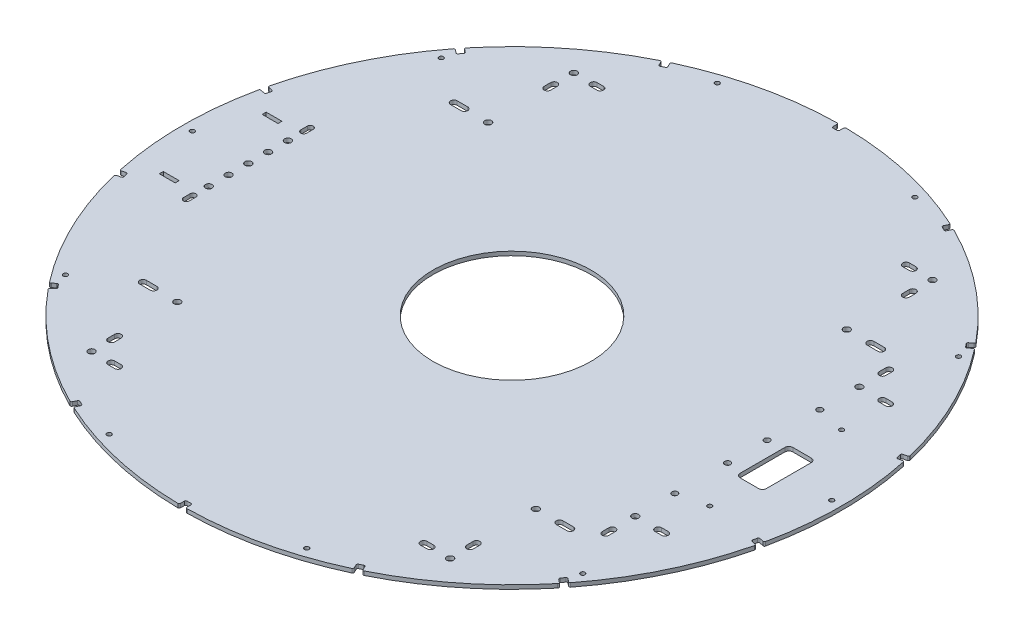
SolidWorks part; units mm, degrees
ref_plane "Front Plane" through (0, 0, 0) normal (0, 0, 1) x (1, 0, 0)
ref_plane "Top Plane" through (0, 0, 0) normal (0, 1, 0) x (1, 0, 0)
ref_plane "Right Plane" through (0, 0, 0) normal (1, 0, 0) x (0, 0, -1)
sketch "Sketch1" plane through (0, 0, 0) normal (0, 1, 0) x (1, 0, 0)
  circle A0 centre (0, 0) radius 250
extrude "Boss-Extrude1" add sketch "Sketch1" along normal blind 3
sketch "Sketch11" plane through (0, 3, 0) normal (0, 1, 0) x (1, 0, 0)
  line L1 (1.5, 245) -> (-1.5, 245)
  line L2 (2.5, 246) -> (2.5, 255)
  line L3 (2.5, 255) -> (-2.5, 255)
  line L4 (-2.5, 246) -> (-2.5, 255)
  line L5 (2.5, 245) -> (-2.5, 255) construction
  line L6 (2.5, 255) -> (-2.5, 245) construction
  circle A0 centre (0, 0) radius 250 construction
  arc A1 (2.5, 246) -> (1.5, 245) centre (1.5, 246) cw
  arc A2 (-1.5, 245) -> (-2.5, 246) centre (-1.5, 246) cw
  point P0 (0, 250)
  dimension "D3" = 1
  dimension "D1" = 10
  dimension "D2" = 5
extrude "Cut-Extrude5" cut sketch "Sketch11" against normal blind 4
fillet "Fillet1" radius 1 2 edges at (2.5, 1.5, -249.9875) (-2.5, 1.5, -249.9875)
pattern_circular "CirPattern1" count 14 over 360 about axis through (0, 3, 0) along (0, -1, 0) of "Cut-Extrude5", "Fillet1"
sketch "Sketch20" plane through (0, 0, 0) normal (0, -1, 0) x (1, 0, 0)
  line L0 (-166.5, -117.9) -> (-148.647, -117.9) construction
  line L1 (-162, -117.9) -> (-154, -117.9) construction
  line L2 (-162, -115.4) -> (-154, -115.4)
  line L3 (-162, -120.4) -> (-154, -120.4)
  line L4 (0, -1.65) -> (0, 1.65) construction
  line L5 (166.5, -117.9) -> (148.647, -117.9) construction
  line L6 (162, -117.9) -> (154, -117.9) construction
  line L7 (162, -115.4) -> (154, -115.4)
  line L8 (162, -120.4) -> (154, -120.4)
  line L9 (1.65, 0) -> (-1.65, 0) construction
  line L10 (162, 117.9) -> (154, 117.9) construction
  line L11 (162, 115.4) -> (154, 115.4)
  line L12 (162, 120.4) -> (154, 120.4)
  line L13 (-162, 117.9) -> (-154, 117.9) construction
  line L14 (-162, 115.4) -> (-154, 115.4)
  line L15 (-162, 120.4) -> (-154, 120.4)
  line L16 (-166.5, 117.9) -> (-148.647, 117.9) construction
  line L17 (166.5, 117.9) -> (148.647, 117.9) construction
  arc A0 (-164, -115.4) -> (-164, -120.4) centre (-164, -117.9) ccw construction
  arc A1 (-162, -115.4) -> (-162, -120.4) centre (-162, -117.9) ccw
  arc A2 (-154, -120.4) -> (-154, -115.4) centre (-154, -117.9) ccw
  arc A3 (162, -115.4) -> (162, -120.4) centre (162, -117.9) cw
  arc A4 (154, -120.4) -> (154, -115.4) centre (154, -117.9) cw
  arc A5 (162, 115.4) -> (162, 120.4) centre (162, 117.9) ccw
  arc A6 (154, 120.4) -> (154, 115.4) centre (154, 117.9) ccw
  arc A7 (-162, 115.4) -> (-162, 120.4) centre (-162, 117.9) cw
  arc A8 (-154, 120.4) -> (-154, 115.4) centre (-154, 117.9) cw
  point P8 (-158, -117.9)
  point P20 (158, -117.9)
  point P29 (158, 117.9)
  point P36 (-158, 117.9)
  dimension "D1" = 2.5
  dimension "D2" = 8
  dimension "D3" = 158
extrude "Cut-Extrude14" cut sketch "Sketch20" against normal blind 14
sketch "Sketch22" plane through (0, 3, 0) normal (0, 1, 0) x (1, 0, 0)
  line L0 (-1.65, 0) -> (1.65, 0) construction
  line L1 (0, -1.65) -> (0, 1.65) construction
  circle A0 centre (-136, -117.9) radius 2.5
  circle A1 centre (-136, 117.9) radius 2.5
  circle A2 centre (136, 117.9) radius 2.5
  circle A3 centre (136, -117.9) radius 2.5
  circle A4 centre (-136, 182.9) radius 2.5
  circle A5 centre (136, 182.9) radius 2.5
  circle A6 centre (-136, -182.9) radius 2.5
  circle A7 centre (136, -182.9) radius 2.5
  dimension "D1" = 2
extrude "Cut-Extrude16" cut sketch "Sketch22" against normal blind 14
sketch "Sketch26" plane through (0, 3, 0) normal (0, 1, 0) x (1, 0, 0)
  line L0 (-136, 162.9) -> (-136, 167.9) construction
  line L1 (-138.5, 162.9) -> (-138.5, 167.9)
  line L2 (-133.5, 162.9) -> (-133.5, 167.9)
  line L3 (-116, 182.9) -> (-121, 182.9) construction
  line L4 (-116, 180.4) -> (-121, 180.4)
  line L5 (-116, 185.4) -> (-121, 185.4)
  line L6 (0, -1.65) -> (0, 1.65) construction
  line L7 (116, 182.9) -> (121, 182.9) construction
  line L8 (116, 180.4) -> (121, 180.4)
  line L9 (116, 185.4) -> (121, 185.4)
  line L10 (136, 162.9) -> (136, 167.9) construction
  line L11 (138.5, 162.9) -> (138.5, 167.9)
  line L12 (133.5, 162.9) -> (133.5, 167.9)
  line L13 (-1.65, 0) -> (1.65, 0) construction
  line L14 (116, -182.9) -> (121, -182.9) construction
  line L15 (116, -180.4) -> (121, -180.4)
  line L16 (116, -185.4) -> (121, -185.4)
  line L17 (136, -162.9) -> (136, -167.9) construction
  line L18 (138.5, -162.9) -> (138.5, -167.9)
  line L19 (133.5, -162.9) -> (133.5, -167.9)
  line L20 (-136, -162.9) -> (-136, -167.9) construction
  line L21 (-138.5, -162.9) -> (-138.5, -167.9)
  line L22 (-133.5, -162.9) -> (-133.5, -167.9)
  line L23 (-116, -182.9) -> (-121, -182.9) construction
  line L24 (-116, -180.4) -> (-121, -180.4)
  line L25 (-116, -185.4) -> (-121, -185.4)
  arc A0 (-138.5, 162.9) -> (-133.5, 162.9) centre (-136, 162.9) ccw
  arc A1 (-133.5, 167.9) -> (-138.5, 167.9) centre (-136, 167.9) ccw
  circle A2 centre (-136, 182.9) radius 2.5 construction
  arc A3 (-116, 180.4) -> (-116, 185.4) centre (-116, 182.9) ccw
  arc A4 (-121, 185.4) -> (-121, 180.4) centre (-121, 182.9) ccw
  arc A5 (116, 180.4) -> (116, 185.4) centre (116, 182.9) cw
  arc A6 (121, 185.4) -> (121, 180.4) centre (121, 182.9) cw
  arc A7 (138.5, 162.9) -> (133.5, 162.9) centre (136, 162.9) cw
  arc A8 (133.5, 167.9) -> (138.5, 167.9) centre (136, 167.9) cw
  arc A9 (116, -180.4) -> (116, -185.4) centre (116, -182.9) ccw
  arc A10 (121, -185.4) -> (121, -180.4) centre (121, -182.9) ccw
  arc A11 (138.5, -162.9) -> (133.5, -162.9) centre (136, -162.9) ccw
  arc A12 (133.5, -167.9) -> (138.5, -167.9) centre (136, -167.9) ccw
  arc A13 (-138.5, -162.9) -> (-133.5, -162.9) centre (-136, -162.9) cw
  arc A14 (-133.5, -167.9) -> (-138.5, -167.9) centre (-136, -167.9) cw
  arc A15 (-116, -180.4) -> (-116, -185.4) centre (-116, -182.9) cw
  arc A16 (-121, -185.4) -> (-121, -180.4) centre (-121, -182.9) cw
  point P3 (-136, 165.4)
  point P12 (-118.5, 182.9)
  point P21 (118.5, 182.9)
  point P28 (136, 165.4)
  point P37 (118.5, -182.9)
  point P44 (136, -165.4)
  point P51 (-136, -165.4)
  point P58 (-118.5, -182.9)
  dimension "D1" = 2.5
  dimension "D4" = 2.5
  dimension "D2" = 5
  dimension "D3" = 17.5
  dimension "D5" = 5
  dimension "D6" = 17.5
extrude "Cut-Extrude19" cut sketch "Sketch26" against normal blind 4
sketch "Sketch28" plane through (0, 3, 0) normal (0, 1, 0) x (1, 0, 0)
  line L0 (-1.65, 0) -> (1.65, 0) construction
  circle A0 centre (-200, 0) radius 2.5
  circle A1 centre (-200, -15) radius 2.5
  circle A2 centre (-200, -30) radius 2.5
  circle A3 centre (-200, 30) radius 2.5
  circle A4 centre (-200, 15) radius 2.5
  dimension "D1" = 200
  dimension "D2" = 3
extrude "Cut-Extrude20" cut sketch "Sketch28" against normal blind 10
sketch "Sketch29" plane through (0, 3, 0) normal (0, 1, 0) x (1, 0, 0)
  line L0 (-200, 42) -> (-200, 47) construction
  line L1 (-202.2, 42) -> (-202.2, 47)
  line L2 (-197.8, 42) -> (-197.8, 47)
  line L3 (-1.65, 0) -> (1.65, 0) construction
  line L4 (-200, -42) -> (-200, -47) construction
  line L5 (-202.2, -42) -> (-202.2, -47)
  line L6 (-197.8, -42) -> (-197.8, -47)
  arc A0 (-202.2, 42) -> (-197.8, 42) centre (-200, 42) ccw
  arc A1 (-197.8, 47) -> (-202.2, 47) centre (-200, 47) ccw
  arc A2 (-202.2, -42) -> (-197.8, -42) centre (-200, -42) cw
  arc A3 (-197.8, -47) -> (-202.2, -47) centre (-200, -47) cw
  point P3 (-200, 44.5)
  point P13 (-200, -44.5)
  dimension "D1" = 2.2
  dimension "D2" = 12
  dimension "D3" = 5
extrude "Cut-Extrude21" cut sketch "Sketch29" against normal blind 10
sketch "Sketch30" plane through (0, 3, 0) normal (0, 1, 0) x (1, 0, 0)
  line L0 (-1.65, 0) -> (1.65, 0) construction
  line L1 (-215, 37.5) -> (-227, 37.5)
  line L2 (-215, 37.5) -> (-215, 40.5)
  line L3 (-215, 40.5) -> (-227, 40.5)
  line L4 (-227, 37.5) -> (-227, 40.5)
  line L5 (-215, 37.5) -> (-227, 40.5) construction
  line L6 (-215, 40.5) -> (-227, 37.5) construction
  line L7 (-215, -40.5) -> (-227, -37.5) construction
  line L8 (-215, -37.5) -> (-227, -40.5) construction
  line L9 (-227, -37.5) -> (-227, -40.5)
  line L10 (-215, -40.5) -> (-227, -40.5)
  line L11 (-215, -37.5) -> (-215, -40.5)
  line L12 (-215, -37.5) -> (-227, -37.5)
  circle A0 centre (-200, 30) radius 2.5 construction
  point P0 (-221, 39)
  point P13 (-221, -39)
  dimension "D1" = 12
  dimension "D2" = 3
  dimension "D3" = 9
  dimension "D4" = 21
extrude "Cut-Extrude22" cut sketch "Sketch30" against normal blind 10
sketch "Sketch31" plane through (0, 3, 0) normal (0, 1, 0) x (1, 0, 0)
  circle A0 centre (178.5, 85) radius 2.5
  circle A1 centre (178.5, -85) radius 2.5
extrude "Cut-Extrude23" cut sketch "Sketch31" against normal blind 10
sketch "Sketch32" plane through (0, 3, 0) normal (0, 1, 0) x (1, 0, 0)
  line L0 (178.5, 107.5) -> (178.5, 102.5) construction
  line L1 (181, 107.5) -> (181, 102.5)
  line L2 (176, 107.5) -> (176, 102.5)
  line L3 (201, 85) -> (196, 85) construction
  line L4 (201, 82.5) -> (196, 82.5)
  line L5 (201, 87.5) -> (196, 87.5)
  line L6 (-1.65, 0) -> (1.65, 0) construction
  line L7 (201, -85) -> (196, -85) construction
  line L8 (201, -82.5) -> (196, -82.5)
  line L9 (201, -87.5) -> (196, -87.5)
  line L10 (178.5, -107.5) -> (178.5, -102.5) construction
  line L11 (181, -107.5) -> (181, -102.5)
  line L12 (176, -107.5) -> (176, -102.5)
  arc A0 (181, 107.5) -> (176, 107.5) centre (178.5, 107.5) ccw
  arc A1 (176, 102.5) -> (181, 102.5) centre (178.5, 102.5) ccw
  circle A2 centre (178.5, 85) radius 2.5 construction
  arc A3 (201, 82.5) -> (201, 87.5) centre (201, 85) ccw
  arc A4 (196, 87.5) -> (196, 82.5) centre (196, 85) ccw
  arc A5 (201, -82.5) -> (201, -87.5) centre (201, -85) cw
  arc A6 (196, -87.5) -> (196, -82.5) centre (196, -85) cw
  arc A7 (181, -107.5) -> (176, -107.5) centre (178.5, -107.5) cw
  arc A8 (176, -102.5) -> (181, -102.5) centre (178.5, -102.5) cw
  point P3 (178.5, 105)
  point P12 (198.5, 85)
  point P21 (198.5, -85)
  point P28 (178.5, -105)
  dimension "D1" = 2.5
  dimension "D3" = 2.5
  dimension "D2" = 20
  dimension "D4" = 20
  dimension "D5" = 5
  dimension "D6" = 5
extrude "Cut-Extrude24" cut sketch "Sketch32" against normal blind 10
sketch "Sketch33" plane through (0, 3, 0) normal (0, 1, 0) x (1, 0, 0)
  line L0 (-1.65, 0) -> (1.65, 0) construction
  circle A0 centre (178.5, 55) radius 2.2
  circle A1 centre (178.5, 85) radius 2.5 construction
  circle A2 centre (178.5, 15) radius 2.2
  circle A3 centre (178.5, -15) radius 2.2
  circle A4 centre (178.5, -55) radius 2.2
  dimension "D1" = 30
extrude "Cut-Extrude25" cut sketch "Sketch33" against normal blind 10
sketch "Sketch34" plane through (0, 3, 0) normal (0, 1, 0) x (1, 0, 0)
  line L1 (207, -20) -> (193, -20)
  line L2 (210, -17) -> (210, 17)
  line L3 (207, 20) -> (193, 20)
  line L4 (190, -17) -> (190, 17)
  line L5 (210, -20) -> (190, 20) construction
  line L6 (210, 20) -> (190, -20) construction
  arc A0 (190, -17) -> (193, -20) centre (193, -17) ccw
  arc A1 (207, -20) -> (210, -17) centre (207, -17) ccw
  arc A2 (210, 17) -> (207, 20) centre (207, 17) ccw
  arc A3 (193, 20) -> (190, 17) centre (193, 17) ccw
  point P0 (200, 0)
  dimension "D5" = 3
  dimension "D1" = 0
  dimension "D2" = 40
  dimension "D3" = 20
  dimension "D4" = 200
extrude "Cut-Extrude26" cut sketch "Sketch34" against normal blind 10
sketch "Sketch35" plane through (0, 3, 0) normal (0, 1, 0) x (1, 0, 0)
  circle A0 centre (0, 0) radius 242.5
  circle A1 centre (-242.5, 0) radius 1.7
extrude "Cut-Extrude27" cut sketch "Sketch35" against normal blind 10 contours A0 A1 | A0 A1 region at (-241.7774, 3, 0) region at (-243.2204, 3, 0)
pattern_circular "CirPattern2" count 10 over 360 about axis through (0, 3, 0) along (0, 1, 0) of "Cut-Extrude27"
sketch "Sketch36" plane through (0, 3, 0) normal (0, 1, 0) x (1, 0, 0)
  circle A0 centre (0, 0) radius 60
extrude "Cut-Extrude28" cut sketch "Sketch36" against normal blind 10
sketch "Sketch37" plane through (0, 3, 0) normal (0, 1, 0) x (1, 0, 0)
  line L0 (207, 20) -> (193, 20) construction
  line L1 (193, -20) -> (207, -20) construction
  circle A0 centre (200, 50) radius 1.7
  circle A1 centre (200, -50) radius 1.7
  dimension "D1" = 30
  dimension "D2" = 30
extrude "Cut-Extrude29" cut sketch "Sketch37" against normal blind 3
